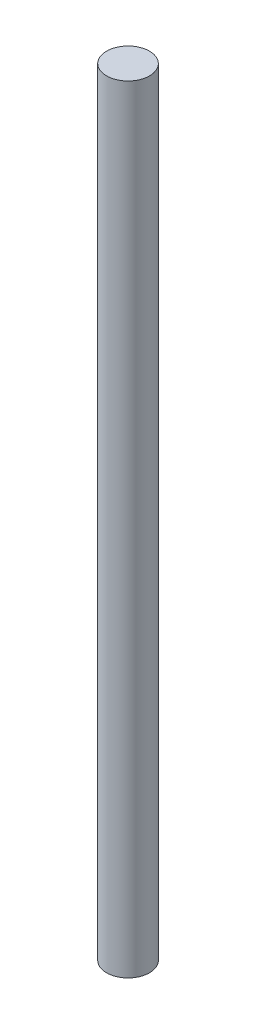
SolidWorks part; units mm, degrees
ref_plane "前视基准面" through (0, 0, 0) normal (0, 0, 1) x (1, 0, 0)
ref_plane "上视基准面" through (0, 0, 0) normal (0, 1, 0) x (1, 0, 0)
ref_plane "右视基准面" through (0, 0, 0) normal (1, 0, 0) x (0, 0, -1)
sketch "草图1" plane through (0, 0, 0) normal (0, 1, 0) x (1, 0, 0)
  circle A0 centre (0, 0) radius 1
  dimension "D1" = 2
extrude "凸台-拉伸1" add sketch "草图1" along normal blind 36.2
